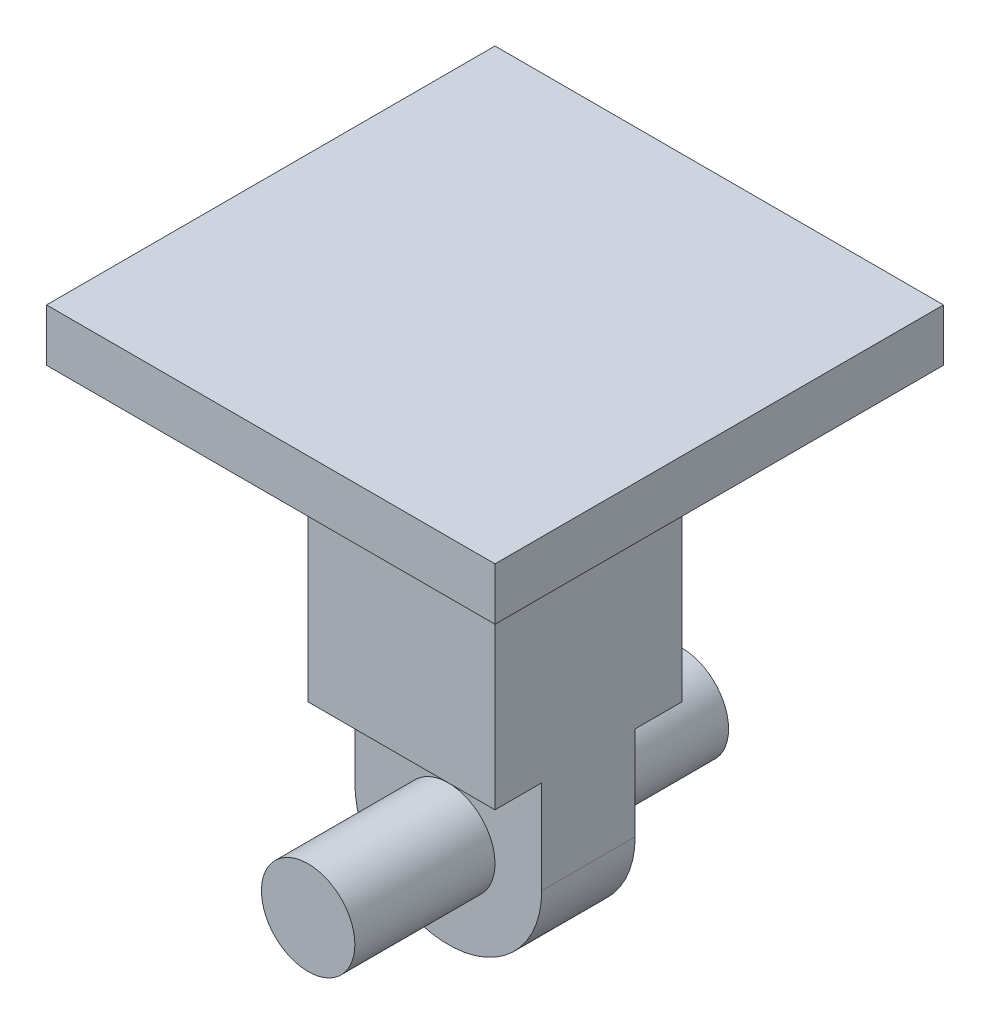
SolidWorks part; units mm, degrees
ref_plane "前视基准面" through (0, 0, 0) normal (0, 0, 1) x (1, 0, 0)
ref_plane "上视基准面" through (0, 0, 0) normal (0, 1, 0) x (1, 0, 0)
ref_plane "右视基准面" through (0, 0, 0) normal (1, 0, 0) x (0, 0, -1)
other "Configuration Table"
sketch "草图1" plane through (0, 0, 0) normal (0, 1, 0) x (1, 0, 0)
  line L1 (-30, -30) -> (30, -30)
  line L2 (-30, -30) -> (-30, 30)
  line L3 (-30, 30) -> (30, 30)
  line L4 (30, -30) -> (30, 30)
  line L5 (-30, -30) -> (30, 30) construction
  line L6 (-30, 30) -> (30, -30) construction
  point P0 (0, 0)
  dimension "D1" = 60
  dimension "D2" = 60
extrude "凸台-拉伸1" add sketch "草图1" along normal blind 7
sketch "草图3" plane through (0, 0, 0) normal (0, 1, 0) x (1, 0, 0)
  line L1 (-12.5, -12.5) -> (12.5, -12.5)
  line L2 (-12.5, -12.5) -> (-12.5, 12.5)
  line L3 (-12.5, 12.5) -> (12.5, 12.5)
  line L4 (12.5, -12.5) -> (12.5, 12.5)
  line L5 (-12.5, -12.5) -> (12.5, 12.5) construction
  line L6 (-12.5, 12.5) -> (12.5, -12.5) construction
  point P0 (0, 0)
  dimension "D1" = 25
  dimension "D2" = 25
extrude "凸台-拉伸2" add sketch "草图3" against normal blind 51.5
sketch "草图4" plane through (0, 0, 0) normal (0, 0, 1) x (1, 0, 0)
  line L0 (-12.5, -51.5) -> (12.5, -51.5) construction
  line L1 (12.5, -51.5) -> (-12.5, -51.5)
  arc A0 (-12.5, -51.5) -> (12.5, -51.5) centre (0, -51.5) ccw
extrude "凸台-拉伸3" add sketch "草图4" against normal up to surface (12.5 mm away) from surface up to face at (0, -25.75, -12.5) starting at face at (0, -25.75, 12.5)
sketch "草图7" plane through (0, 0, 0) normal (0, 1, 0) x (1, 0, 0)
  line L0 (12.5, -12.5) -> (12.5, 12.5) construction
  line L5 (-12.5, 12.5) -> (12.5, 12.5)
  line L6 (-12.5, 12.5) -> (-12.5, 6.25)
  line L7 (-12.5, 6.25) -> (12.5, 6.25)
  line L8 (12.5, 12.5) -> (12.5, 6.25)
  line L10 (-12.5, -12.5) -> (12.5, -12.5)
  line L11 (-12.5, -12.5) -> (-12.5, -6.25)
  line L12 (-12.5, -6.25) -> (12.5, -6.25)
  line L13 (12.5, -12.5) -> (12.5, -6.25)
  dimension "D1" = 6.25
  dimension "D2" = 6.25
extrude "切除-拉伸3" cut sketch "草图7" against normal blind 12.5 and the other way blind 12.5 from vertex starting at point (12.5, -51.5, 12.5)
sketch "草图8" plane through (0, 0, 0) normal (0, 0, 1) x (1, 0, 0)
  arc A0 (-12.5, -51.5) -> (12.5, -51.5) centre (0, -51.5) ccw construction
  arc A1 (-12.5, -51.5) -> (12.5, -51.5) centre (0, -51.5) ccw construction
  circle A2 centre (0, -51.5) radius 6.25
  dimension "D1" = 12.5
extrude "凸台-拉伸4" add sketch "草图8" against normal blind 25 and the other way blind 25
sketch "草图10" plane through (0, 0, 0) normal (1, 0, 0) x (0, 0, -1)
  line L0 (-75, -51.5) -> (75, -51.5)
  line L2 (25, -57.75) -> (25, -45.25) construction
  line L4 (25, -57.75) -> (25, -45.25) construction
  point P3 (0, -51.5)
  point P7 (25, -51.5)
  dimension "D1" = 150
sketch "草图11" plane through (0, 0, 0) normal (1, 0, 0) x (0, 0, -1)
  line L0 (0, -201.5) -> (0, 98.5)
  point P4 (0, -51.5)
  dimension "D1" = 300
